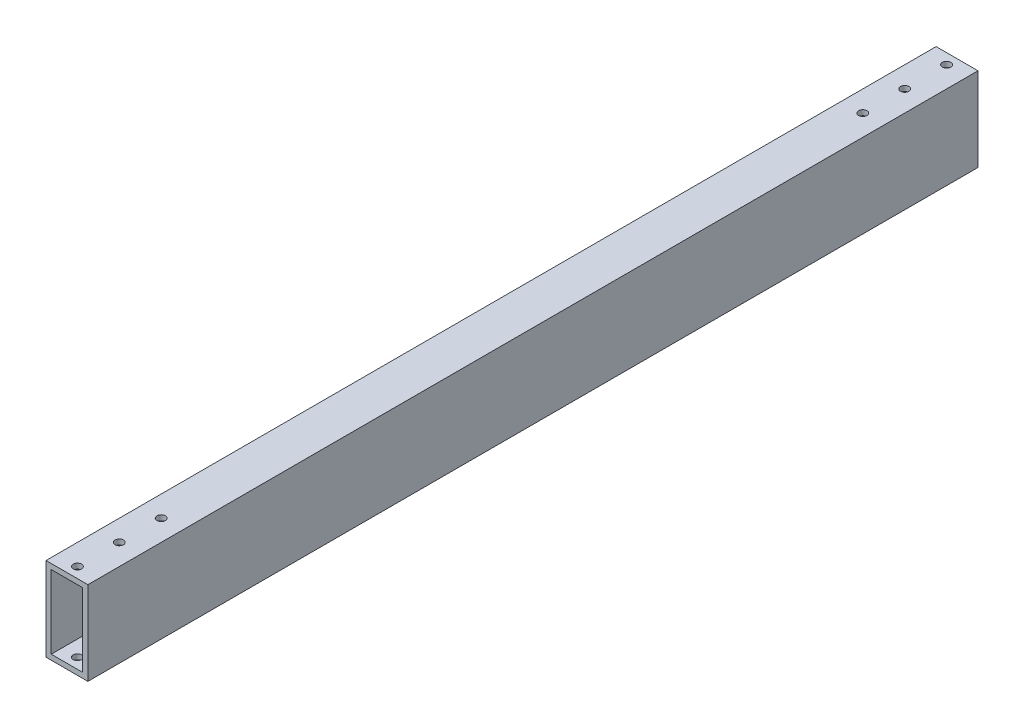
SolidWorks part; units mm, degrees
material "6061-T6 (SS)"
ref_plane "Front" through (0, 0, 0) normal (0, 0, 1) x (1, 0, 0)
ref_plane "Top" through (0, 0, 0) normal (0, 1, 0) x (1, 0, 0)
ref_plane "Right" through (0, 0, 0) normal (1, 0, 0) x (0, 0, -1)
sketch "Sketch1" plane through (0, 0, 0) normal (0, 0, 1) x (1, 0, 0)
  line L1 (-12.7, -25.4) -> (12.7, -25.4)
  line L2 (-12.7, -25.4) -> (-12.7, 25.4)
  line L3 (-12.7, 25.4) -> (12.7, 25.4)
  line L4 (12.7, -25.4) -> (12.7, 25.4)
  line L5 (-12.7, -25.4) -> (12.7, 25.4) construction
  line L6 (-12.7, 25.4) -> (12.7, -25.4) construction
  point P0 (0, 0)
  dimension "D1" = 25.4
  dimension "D2" = 50.8
extrude "Extrude-Thin1" add sketch "Sketch1" along normal blind 539.75 thin thin type one direction reverse wall 3.175
hole_wizard "#10 Clearance Hole2" positions "Sketch4" profile "Sketch5" hole size "#10" standard "ANSI Inch" end condition through all
sketch "Sketch4" plane through (0, 25.4, 0) normal (0, 1, 0) x (1, 0, 0)
  line L0 (12.7, -539.75) -> (-12.7, -539.75) construction
  line L1 (-12.7, -539.75) -> (-12.7, 0) construction
  line L2 (12.7, 0) -> (-12.7, 0) construction
  point P0 (0, -533.4)
  point P2 (0, -508)
  point P4 (0, -482.6)
  point P6 (0, -533.4)
  point P8 (0, -508)
  point P10 (0, -533.4)
  point P23 (0, -6.35)
  point P25 (0, -31.75)
  point P27 (0, -57.15)
  dimension "D1" = 6.35
  dimension "D2" = 25.4
  dimension "D3" = 25.4
  dimension "D4" = 12.7
  dimension "D5" = 6.35
  dimension "D6" = 25.4
  dimension "D7" = 25.4
sketch "Sketch5" plane through (0, 25.4, 533.4) normal (1, 0, 0) x (0, 0, 1)
  line L0 (0, 0) -> (0, 50.8)
  line L1 (0, 50.8) -> (2.5527, 50.8)
  line L2 (2.5527, 50.8) -> (2.5527, 0)
  line L5 (2.5527, 0) -> (0, 0)
  line L11 (0, -6.35) -> (0, 107.95) construction
  dimension "Thru Hole Dia." = 5.1054
  dimension "Thru Hole Depth" = 50.8
